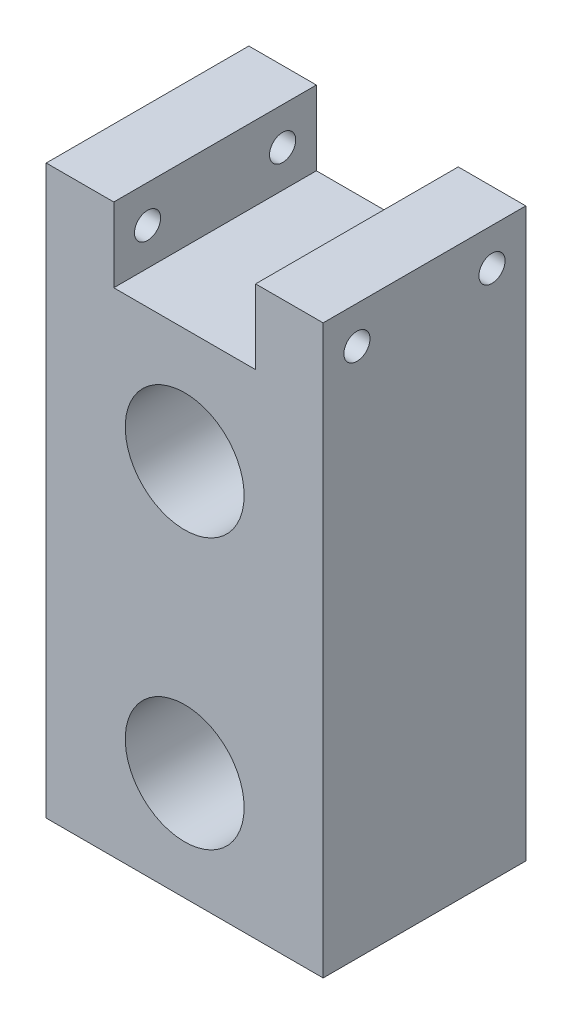
SolidWorks part; units mm, degrees
ref_plane "Front Plane" through (0, 0, 0) normal (0, 0, 1) x (1, 0, 0)
ref_plane "Top Plane" through (0, 0, 0) normal (0, 1, 0) x (1, 0, 0)
ref_plane "Right Plane" through (0, 0, 0) normal (1, 0, 0) x (0, 0, -1)
sketch "Sketch1" plane through (0, 0, 0) normal (0, 0, 1) x (1, 0, 0)
  line L0 (13.335, 21.59) -> (-13.335, 21.59)
  line L1 (-13.335, 21.59) -> (-13.335, 35.56)
  line L2 (-13.335, 35.56) -> (-26.035, 35.56)
  line L3 (-26.035, 35.56) -> (-26.035, -71.12)
  line L4 (-26.035, -71.12) -> (26.035, -71.12)
  line L5 (0, 0) -> (0, 45.5255) construction
  line L6 (26.035, 35.56) -> (26.035, -71.12)
  line L7 (13.335, 35.56) -> (26.035, 35.56)
  line L8 (13.335, 21.59) -> (13.335, 35.56)
  point P7 (0, -71.12)
  point P15 (0, 21.59)
  dimension "D1" = 21.59
  dimension "D2" = 13.97
  dimension "D3" = 12.7
  dimension "D4" = 71.12
  dimension "D5" = 13.335
extrude "Boss-Extrude1" add sketch "Sketch1" along normal mid plane 38.1
sketch "Sketch2" plane through (0, 0, 19.05) normal (0, 0, 1) x (1, 0, 0)
  circle A0 centre (0, 0) radius 11.176
  circle A1 centre (0, -50.8) radius 11.176
  point P4 (0, 0)
  dimension "D1" = 22.352
  dimension "D3" = 22.352
  dimension "D2" = 50.8
extrude "Cut-Extrude1" cut sketch "Sketch2" against normal up to surface (38.1 mm away) up to face at (0, 5.3975, -19.05)
hole_wizard "#10 (0.1935) Diameter Hole1" positions "Sketch5" profile "Sketch6" hole size "#10" standard "ANSI Inch" end condition through all
sketch "Sketch5" plane through (26.035, 0, 0) normal (1, 0, 0) x (0, 0, -1)
  point P0 (-12.7, 28.575)
  dimension "D1" = 12.7
  dimension "D2" = 28.575
sketch "Sketch6" plane through (26.035, 28.575, 12.7) normal (0, 1, 0) x (0, 0, -1)
  line L0 (0, 0) -> (0, 52.07)
  line L1 (0, 52.07) -> (2.4574, 52.07)
  line L2 (2.4574, 52.07) -> (2.4574, 0)
  line L5 (2.4574, 0) -> (0, 0)
  line L11 (0, -6.35) -> (0, 107.95) construction
  dimension "Thru Hole Dia." = 4.9149
  dimension "Thru Hole Depth" = 52.07
mirror "Mirror1" about plane through (0, 0, 0) normal (0, 0, 1) of "#10 (0.1935) Diameter Hole1"
